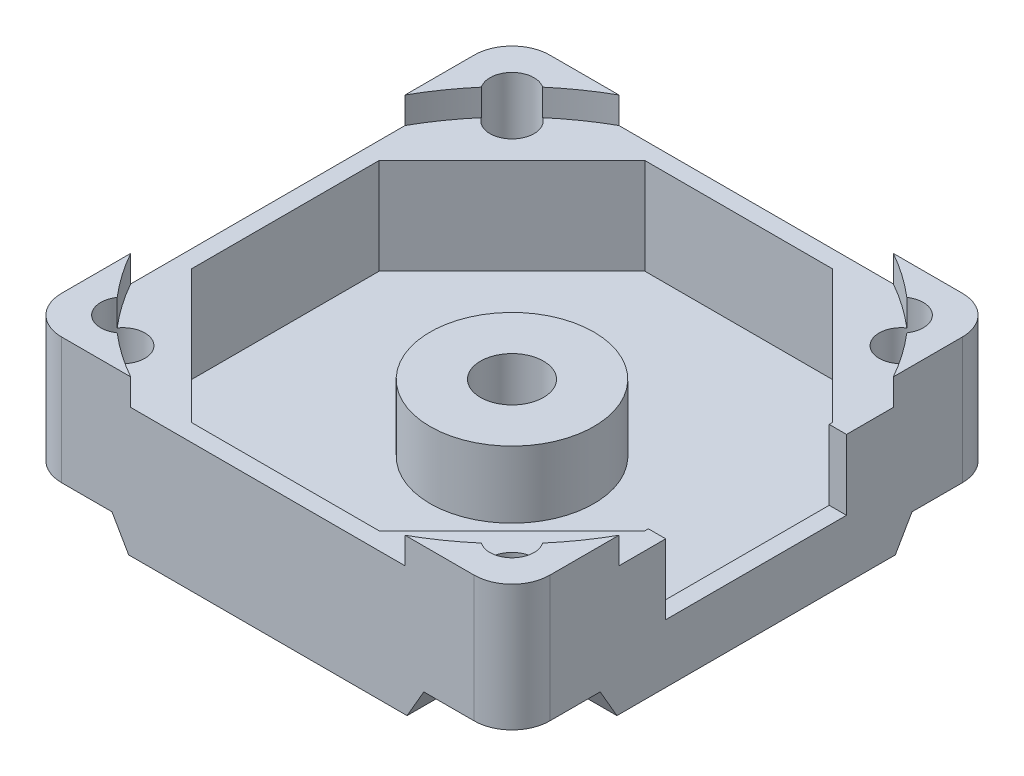
SolidWorks part; units mm, degrees
ref_plane "Front Plane" through (0, 0, 0) normal (0, 0, 1) x (1, 0, 0)
ref_plane "Top Plane" through (0, 0, 0) normal (0, 1, 0) x (1, 0, 0)
ref_plane "Right Plane" through (0, 0, 0) normal (1, 0, 0) x (0, 0, -1)
sketch "Sketch1" plane through (0, 0, 0) normal (0, 1, 0) x (1, 0, 0)
  line L1 (-16.375, -19.375) -> (16.375, -19.375)
  line L2 (-19.375, -16.375) -> (-19.375, 16.375)
  line L3 (-16.375, 19.375) -> (16.375, 19.375)
  line L4 (19.375, -16.375) -> (19.375, 16.375)
  line L5 (-19.375, -19.375) -> (19.375, 19.375) construction
  line L6 (-19.375, 19.375) -> (19.375, -19.375) construction
  line L7 (-15.445, 15.445) -> (15.445, 15.445) construction
  line L8 (-15.445, 15.445) -> (-15.445, -15.445) construction
  line L9 (-15.445, -15.445) -> (15.445, -15.445) construction
  line L10 (15.445, 15.445) -> (15.445, -15.445) construction
  circle A0 centre (0, 0) radius 2.5
  arc A1 (16.375, -19.375) -> (19.375, -16.375) centre (16.375, -16.375) ccw
  arc A2 (-16.375, -19.375) -> (-19.375, -16.375) centre (-16.375, -16.375) cw
  arc A3 (16.375, 19.375) -> (19.375, 16.375) centre (16.375, 16.375) cw
  arc A4 (-19.375, 16.375) -> (-16.375, 19.375) centre (-16.375, 16.375) cw
  circle A5 centre (-15.445, 15.445) radius 1.75
  circle A6 centre (15.445, 15.445) radius 1.75
  circle A7 centre (15.445, -15.445) radius 1.75
  circle A8 centre (-15.445, -15.445) radius 1.75
  point P0 (0, 0)
  point P28 (-12.5297, -12.5297)
  dimension "D2" = 5
  dimension "D3" = 3
  dimension "D4" = 3.5
  dimension "D1" = 38.75
  dimension "D5" = 43.685
extrude "Boss-Extrude1" add sketch "Sketch1" along normal blind 2.61
sketch "Sketch2" plane through (0, 2.61, 0) normal (0, 1, 0) x (1, 0, 0)
  line L0 (-7.4558, 18) -> (7.4558, 18)
  line L1 (-18, 7.4558) -> (-18, -7.4558)
  line L2 (18, 7.4558) -> (18, -7.4558)
  line L3 (-7.4558, -18) -> (7.4558, -18)
  line L4 (-7.4558, -18) -> (-18, -7.4558)
  line L5 (7.4558, -18) -> (18, -7.4558)
  line L6 (-18, 7.4558) -> (-7.4558, 18)
  line L7 (18, 7.4558) -> (7.4558, 18)
  line L8 (0, -25.4558) -> (0, 25.4558) construction
  line L9 (25.4558, 0) -> (-25.4558, 0) construction
  line L11 (-7.4558, 18) -> (0, 25.4558) construction
  line L12 (0, 25.4558) -> (7.4558, 18) construction
  line L13 (18, 7.4558) -> (25.4558, 0) construction
  line L14 (25.4558, 0) -> (18, -7.4558) construction
  line L15 (7.4558, -18) -> (0, -25.4558) construction
  line L16 (0, -25.4558) -> (-7.4558, -18) construction
  line L17 (-18, 7.4558) -> (-25.4558, 0) construction
  line L18 (-25.4558, 0) -> (-18, -7.4558) construction
  line L19 (-7.4558, 18) -> (-7.4558, -18) construction
  line L20 (7.4558, -18) -> (-18, 7.4558) construction
  line L24 (19.375, -16.375) -> (19.375, 16.375)
  line L25 (16.375, 19.375) -> (-16.375, 19.375)
  line L26 (-19.375, 16.375) -> (-19.375, -16.375)
  line L27 (-16.375, -19.375) -> (16.375, -19.375)
  line L32 (19.375, -16.375) -> (19.375, 16.375)
  line L33 (16.375, 19.375) -> (-16.375, 19.375)
  line L34 (-19.375, 16.375) -> (-19.375, -16.375)
  line L35 (-16.375, -19.375) -> (16.375, -19.375)
  circle A1 centre (-15.445, 15.445) radius 1.75
  circle A2 centre (-15.445, 15.445) radius 1.75
  circle A3 centre (15.445, 15.445) radius 1.75
  circle A4 centre (15.445, 15.445) radius 1.75
  circle A5 centre (15.445, -15.445) radius 1.75
  circle A6 centre (15.445, -15.445) radius 1.75
  circle A7 centre (-15.445, -15.445) radius 1.75
  circle A12 centre (-15.445, -15.445) radius 1.75
  arc A16 (16.375, -19.375) -> (19.375, -16.375) centre (16.375, -16.375) ccw
  arc A17 (19.375, 16.375) -> (16.375, 19.375) centre (16.375, 16.375) ccw
  arc A18 (-16.375, 19.375) -> (-19.375, 16.375) centre (-16.375, 16.375) ccw
  arc A19 (-19.375, -16.375) -> (-16.375, -19.375) centre (-16.375, -16.375) ccw
  arc A20 (16.375, -19.375) -> (19.375, -16.375) centre (16.375, -16.375) ccw
  arc A21 (19.375, 16.375) -> (16.375, 19.375) centre (16.375, 16.375) ccw
  arc A22 (-16.375, 19.375) -> (-19.375, 16.375) centre (-16.375, 16.375) ccw
  arc A23 (-19.375, -16.375) -> (-16.375, -19.375) centre (-16.375, -16.375) ccw
  point P0 (-46.984, 19.1656)
  dimension "D1" = 36
  dimension "D2" = 0
  dimension "D3" = 0
  dimension "D4" = 0
  dimension "D5" = 0
  dimension "D6" = 0
extrude "Boss-Extrude2" add sketch "Sketch2" along normal offset from surface (7.71 mm away) 10.32 up to face at (0, 0, 0)
sketch "Sketch4" plane through (0, 0, 0) normal (0, -1, 0) x (1, 0, 0)
  line L0 (12.375, 19.375) -> (12.375, 15.445)
  line L1 (-16.375, 19.375) -> (16.375, 19.375) construction
  line L2 (15.445, 12.375) -> (19.375, 12.375)
  line L3 (19.375, 16.375) -> (19.375, -16.375) construction
  line L4 (19.375, 12.375) -> (19.375, 16.375)
  line L5 (16.375, 19.375) -> (12.375, 19.375)
  arc A0 (12.375, 15.445) -> (15.445, 12.375) centre (15.445, 15.445) ccw
  arc A1 (19.375, 16.375) -> (16.375, 19.375) centre (16.375, 16.375) ccw
  circle A2 centre (15.445, 15.445) radius 1.75 construction
  point P14 (13.2956, 13.2956)
  point P15 (15.4846, 15.4846)
  dimension "D1" = 7
extrude "Cut-Extrude1" cut sketch "Sketch4" along normal through all draft 30 from offset 2.3 draft outward yes offset against normal yes
pattern_circular "CirPattern1" count 4 over 360 about axis through (0, 2.61, 0) along (0, -1, 0) of "Cut-Extrude1"
sketch "Sketch6" plane through (19.375, 0, 0) normal (1, 0, 0) x (0, 0, -1)
  line L0 (-11.0471, 0) -> (11.0471, 0) construction
  line L1 (-7.175, 20.3288) -> (7.175, 20.3288)
  line L2 (-7.175, 20.3288) -> (-7.175, 4.66)
  line L3 (-7.175, 4.66) -> (7.175, 4.66)
  line L4 (7.175, 20.3288) -> (7.175, 4.66)
  line L5 (-7.175, 20.3288) -> (7.175, 4.66) construction
  line L6 (-7.175, 4.66) -> (7.175, 20.3288) construction
  point P0 (0, 12.4944)
  point P5 (0, 0)
  dimension "D1" = 14.35
  dimension "D2" = 4.66
extrude "Cut-Extrude2" cut sketch "Sketch6" against normal up to next
sketch "Sketch7" plane through (0, 10.32, 0) normal (0, 1, 0) x (1, 0, 0)
  line L16 (19.375, -7.175) -> (18, -7.175)
  line L17 (18, -7.175) -> (18, -7.4558)
  line L18 (18, -7.4558) -> (7.4558, -18)
  line L19 (7.4558, -18) -> (-7.4558, -18)
  line L20 (-7.4558, -18) -> (-18, -7.4558)
  line L21 (-18, -7.4558) -> (-18, 7.4558)
  line L22 (-18, 7.4558) -> (-7.4558, 18)
  line L23 (-7.4558, 18) -> (7.4558, 18)
  line L24 (7.4558, 18) -> (18, 7.4558)
  line L25 (18, 7.4558) -> (18, 7.175)
  line L26 (18, 7.175) -> (19.375, 7.175)
  line L27 (19.375, 7.175) -> (19.375, 16.375)
  line L28 (16.375, 19.375) -> (-16.375, 19.375)
  line L29 (-19.375, 16.375) -> (-19.375, -16.375)
  line L30 (-16.375, -19.375) -> (16.375, -19.375)
  line L31 (19.375, -16.375) -> (19.375, -7.175)
  line L32 (19.375, -7.175) -> (18, -7.175)
  line L33 (18, -7.175) -> (18, -7.4558)
  line L34 (18, -7.4558) -> (7.4558, -18)
  line L35 (7.4558, -18) -> (-7.4558, -18)
  line L36 (-7.4558, -18) -> (-18, -7.4558)
  line L37 (-18, -7.4558) -> (-18, 7.4558)
  line L38 (-18, 7.4558) -> (-7.4558, 18)
  line L39 (-7.4558, 18) -> (7.4558, 18)
  line L40 (7.4558, 18) -> (18, 7.4558)
  line L41 (18, 7.4558) -> (18, 7.175)
  line L42 (18, 7.175) -> (19.375, 7.175)
  line L43 (19.375, 7.175) -> (19.375, 16.375)
  line L44 (16.375, 19.375) -> (-16.375, 19.375)
  line L45 (-19.375, 16.375) -> (-19.375, -16.375)
  line L46 (-16.375, -19.375) -> (16.375, -19.375)
  line L47 (19.375, -16.375) -> (19.375, -7.175)
  circle A1 centre (-15.445, -15.445) radius 1.75
  circle A2 centre (-15.445, -15.445) radius 1.75
  circle A3 centre (15.445, -15.445) radius 1.75
  circle A4 centre (15.445, -15.445) radius 1.75
  circle A5 centre (15.445, 15.445) radius 1.75
  circle A6 centre (15.445, 15.445) radius 1.75
  circle A7 centre (-15.445, 15.445) radius 1.75
  circle A8 centre (-15.445, 15.445) radius 1.75
  arc A12 (19.375, 16.375) -> (16.375, 19.375) centre (16.375, 16.375) ccw
  arc A13 (-16.375, 19.375) -> (-19.375, 16.375) centre (-16.375, 16.375) ccw
  arc A14 (-19.375, -16.375) -> (-16.375, -19.375) centre (-16.375, -16.375) ccw
  arc A15 (16.375, -19.375) -> (19.375, -16.375) centre (16.375, -16.375) ccw
  arc A16 (19.375, 16.375) -> (16.375, 19.375) centre (16.375, 16.375) ccw
  arc A17 (-16.375, 19.375) -> (-19.375, 16.375) centre (-16.375, 16.375) ccw
  arc A18 (-19.375, -16.375) -> (-16.375, -19.375) centre (-16.375, -16.375) ccw
  arc A19 (16.375, -19.375) -> (19.375, -16.375) centre (16.375, -16.375) ccw
  dimension "D1" = 0
  dimension "D2" = 0
  dimension "D3" = 0
  dimension "D4" = 0
  dimension "D5" = 0
extrude "Boss-Extrude3" add sketch "Sketch7" along normal blind 2
ref_axis "Axis1" through (15.445, 12.32, 15.445) along (0, -1, 0)
ref_axis "Axis2" through (-15.445, 12.32, -15.445) along (0, -1, 0)
ref_plane "Plane1" through (0, 0, 0) normal (-0.7071, 0, 0.7071) x (0.7071, 0, 0.7071)
sketch "Sketch9" plane through (0, 0, 0) normal (-0.7071, 0, 0.7071) x (0.7071, 0, 0.7071)
  line L0 (22.225, 12.32) -> (22.225, 10.22)
  line L1 (22.225, 10.22) -> (6.0526, 10.22)
  line L2 (6.0526, 10.22) -> (6.0526, 12.32)
  line L3 (6.0526, 12.32) -> (22.225, 12.32)
  line L4 (1.75, 12.32) -> (-1.75, 12.32) construction
  line L5 (0, 0) -> (0, 15.3688) construction
  dimension "D1" = 44.45
  dimension "D2" = 2.1
revolve "Cut-Revolve1" cut sketch "Sketch9" angle 360 about L5
sketch "Sketch10" plane through (0, 2.61, 0) normal (0, 1, 0) x (1, 0, 0)
  circle A0 centre (0, 0) radius 6.5
  circle A1 centre (0, 0) radius 2.5
  circle A2 centre (0, 0) radius 2.5
  dimension "D2" = 13
  dimension "D1" = 0
extrude "Boss-Extrude4" add sketch "Sketch10" along normal blind 5.3
